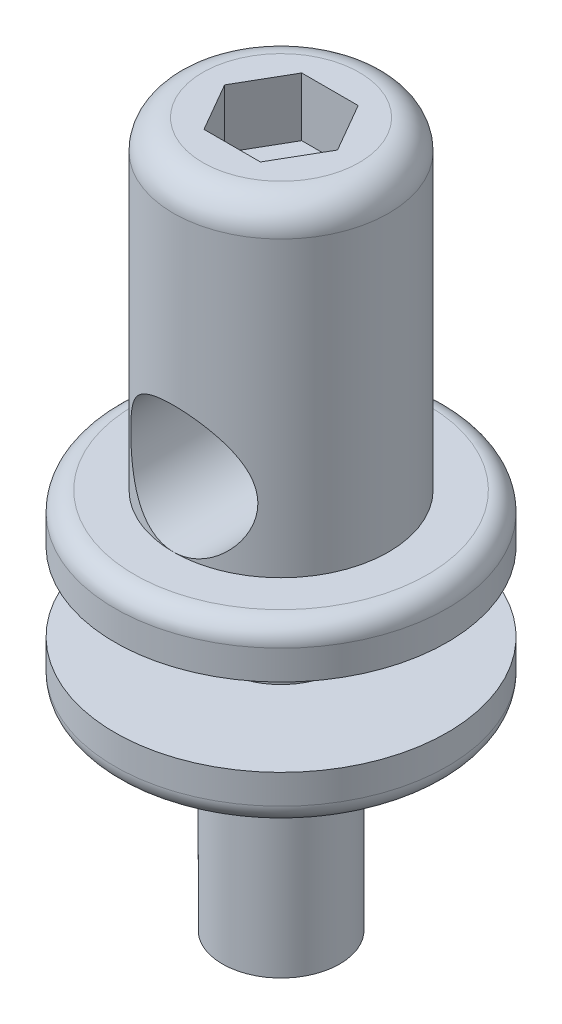
SolidWorks part; units mm, degrees
ref_plane "Piano frontale" through (0, 0, 0) normal (0, 0, 1) x (1, 0, 0)
ref_plane "Piano superiore" through (0, 0, 0) normal (0, 1, 0) x (1, 0, 0)
ref_plane "Piano destro" through (0, 0, 0) normal (1, 0, 0) x (0, 0, -1)
sketch "Schizzo1" plane through (0, 0, 0) normal (0, 1, 0) x (1, 0, 0)
  circle A0 centre (0, 0) radius 5.5
  dimension "D1" = 11
extrude "Estrusione1" add sketch "Schizzo1" along normal blind 19
sketch "Schizzo2" plane through (0, 0, 0) normal (0, -1, 0) x (1, 0, 0)
  circle A0 centre (0, 0) radius 3
  dimension "D1" = 6
extrude "Estrusione2" add sketch "Schizzo2" along normal blind 17
sketch "Schizzo3" plane through (0, 19, 0) normal (0, 1, 0) x (-1, 0, 0)
  line L1 (-2.8868, 0) -> (-1.4434, -2.5)
  line L2 (-1.4434, -2.5) -> (1.4434, -2.5)
  line L3 (1.4434, -2.5) -> (2.8868, 0)
  line L4 (2.8868, 0) -> (1.4434, 2.5)
  line L5 (1.4434, 2.5) -> (-1.4434, 2.5)
  line L6 (-1.4434, 2.5) -> (-2.8868, 0)
  circle A0 centre (0, 0) radius 2.5 construction
extrude "Taglio-Estrusione1" cut sketch "Schizzo3" against normal blind 3
fillet "Raccordo1" radius 1.5 1 edges at (0, 19, 5.5)
sketch "Schizzo4" plane through (0, 0, 0) normal (0, 0, 1) x (1, 0, 0)
  line L0 (0, 19) -> (0, 9) construction
  line L1 (-1.4434, 19) -> (1.4434, 19) construction
  line L4 (-5.5, 0) -> (5.5, 0) construction
  circle A0 centre (0, 5.75) radius 3.25
  dimension "D2" = 6.5
  dimension "D1" = 10
extrude "Taglio-Estrusione2" cut sketch "Schizzo4" against normal through all and the other way through all
sketch "Schizzo5" plane through (0, 0, 0) normal (0, -1, 0) x (1, 0, 0)
  circle A0 centre (0, 0) radius 8.5
  circle A1 centre (0, 0) radius 5.5 construction
  circle A2 centre (0, 0) radius 5.5
  dimension "D1" = 17
extrude "Estrusione3" add sketch "Schizzo5" against normal blind 2.5 separate body
fillet "Raccordo2" radius 1 1 edges at (0, 2.5, -8.5)
ref_plane "Piano1" through (0, -4, 0) normal (0, -1, 0) x (1, 0, 0)
sketch "Schizzo6" plane through (0, -4, 0) normal (0, -1, 0) x (1, 0, 0)
  circle A0 centre (0, 0) radius 3 construction
  circle A1 centre (0, 0) radius 8.5 construction
  circle A2 centre (0, 0) radius 3
  circle A3 centre (0, 0) radius 8.5
extrude "Estrusione4" add sketch "Schizzo6" along normal blind 2.5 separate body
fillet "Raccordo3" radius 1 1 edges at (0, -6.5, -8.5)
ref_axis "Asse1" through (0, 5.75, 5.5) along (0, 0, -1)
